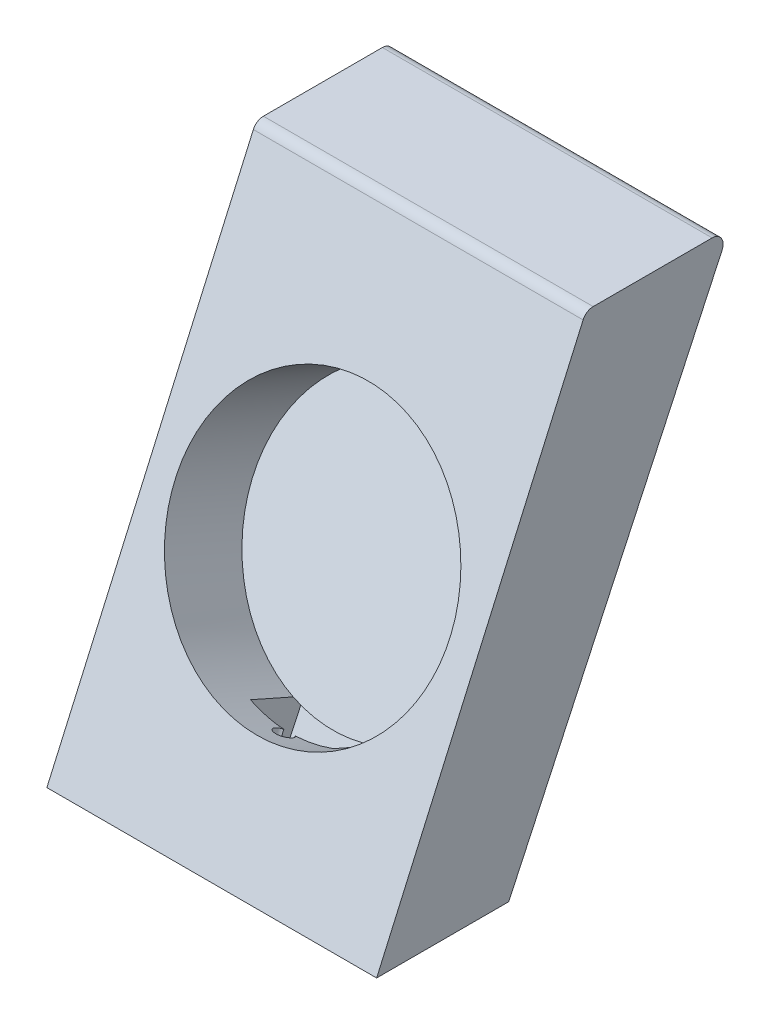
SolidWorks part; units mm, degrees
ref_plane "Front Plane" through (0, 0, 0) normal (0, 0, 1) x (1, 0, 0)
ref_plane "Top Plane" through (0, 0, 0) normal (0, 1, 0) x (1, 0, 0)
ref_plane "Right Plane" through (0, 0, 0) normal (1, 0, 0) x (0, 0, -1)
sketch "Sketch1" plane through (0, 0, 0) normal (1, 0, 0) x (0, 0, -1)
  line L0 (0, 0) -> (30.5248, 0)
  line L1 (30.5248, 0) -> (81.5137, 109.346)
  line L2 (81.5137, 109.346) -> (48.3804, 109.346)
  line L3 (48.3804, 109.346) -> (0, 0)
  line L4 (0, 0) -> (96.4167, 0) construction
  dimension "D1" = 65
extrude "Boss-Extrude1" add sketch "Sketch1" along normal blind 76.2
fillet "Fillet1" radius 2.54 2 edges at (38.1, 109.346, -81.5137) (38.1, 109.346, -48.3804)
sketch "Sketch2" plane through (0, 0, 0) normal (0, 0.4046, 0.9145) x (1, 0, 0)
  line L0 (0, 117.9173) -> (0, 0) construction
  circle A0 centre (37.9129, 58.0879) radius 31.75
  dimension "D1" = 37.9129
  dimension "D2" = 63.5
extrude "Cut-Extrude1" cut sketch "Sketch2" against normal offset from surface (19.1894 mm away) 9 up to face at (38.1, 52.8663, -55.1768)
ref_plane "Plane1" through (0, 0, 0) normal (0, -0.9063, 0.4226) x (-1, 0, 0)
sketch "Sketch6" plane through (0, 0, 0) normal (0, -0.9063, 0.4226) x (-1, 0, 0)
  line L0 (-76.2, 0) -> (0, 0) construction
  circle A0 centre (-37.7623, 6.35) radius 2
  dimension "D1" = 6.35
  dimension "D2" = 4
extrude "Cut-Extrude2" cut sketch "Sketch6" against normal up to surface (26.5086 mm away) up to face at (37.9129, 16.3214, -28.2052)
sketch "Sketch7" plane through (0, 0, 0) normal (0, -0.9063, 0.4226) x (-1, 0, 0)
  line L19 (-47.2615, 21.3149) -> (-28.0508, 21.3149)
  line L20 (-47.2615, 21.3149) -> (-47.2615, 7.85)
  line L21 (-47.2615, 7.85) -> (-28.0508, 7.85)
  line L22 (-28.0508, 21.3149) -> (-28.0508, 7.85)
  line L23 (-37.7623, 4.35) -> (-33.5173, 4.35) construction
  line L24 (-76.2, 27.6649) -> (0, 27.6649) construction
  circle A5 centre (-37.7623, 6.35) radius 2 construction
  circle A6 centre (-37.7623, 6.35) radius 2 construction
  dimension "D1" = 3.5
  dimension "D2" = 6.35
extrude "Cut-Extrude5" cut sketch "Sketch7" against normal up to surface (28.3354 mm away) up to face at (38.2186, 22.0945, -15.1607)
